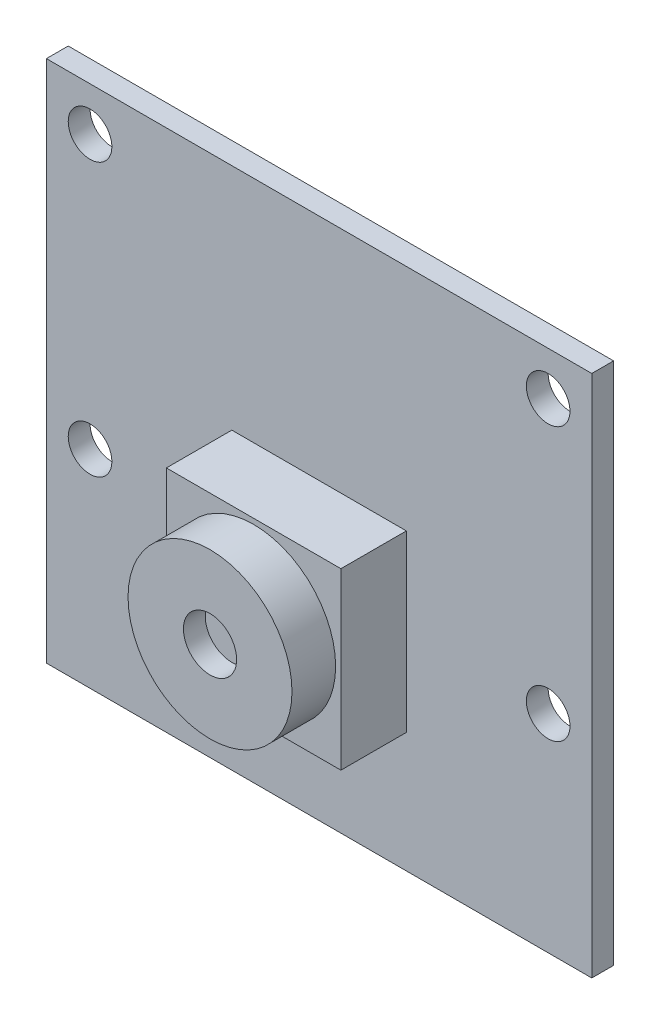
SolidWorks part; units mm, degrees
ref_plane "Front Plane" through (0, 0, 0) normal (0, 0, 1) x (1, 0, 0)
ref_plane "Top Plane" through (0, 0, 0) normal (0, 1, 0) x (1, 0, 0)
ref_plane "Right Plane" through (0, 0, 0) normal (1, 0, 0) x (0, 0, -1)
ref_axis "Axis1" through (-13.75, 0, 0) along (1, 0, 0)
ref_axis "Axis2" through (0, 13.2, 0) along (0, -1, 0)
ref_axis "Axis3" through (0, 0, 6.3) along (0, 0, -1)
ref_point "Point1"
sketch "Sketch1" plane through (0, 0, 0) normal (0, 0, 1) x (1, 0, 0)
  line L1 (-12.5, -12) -> (12.5, -12)
  line L2 (-12.5, -12) -> (-12.5, 12)
  line L3 (-12.5, 12) -> (12.5, 12)
  line L4 (12.5, -12) -> (12.5, 12)
  line L5 (-12.5, -12) -> (12.5, 12) construction
  line L6 (-12.5, 12) -> (12.5, -12) construction
  point P0 (0, 0)
  dimension "D1" = 25
  dimension "D2" = 24
extrude "Boss-Extrude1" add sketch "Sketch1" along normal blind 1
sketch "Sketch2" plane through (0, 0, 1) normal (0, 0, 1) x (1, 0, 0)
  line L0 (-12.5, -12) -> (12.5, -12) construction
  line L1 (-4, -6.5) -> (4, -6.5)
  line L2 (-4, -6.5) -> (-4, 1.5)
  line L3 (-4, 1.5) -> (4, 1.5)
  line L4 (4, -6.5) -> (4, 1.5)
  line L5 (-4, -6.5) -> (4, 1.5) construction
  line L6 (-4, 1.5) -> (4, -6.5) construction
  line L7 (-12.5, 12) -> (-12.5, -12) construction
  point P0 (0, -2.5)
  dimension "D1" = 8
  dimension "D2" = 5.5
  dimension "D3" = 8.5
extrude "Boss-Extrude2" add sketch "Sketch2" along normal blind 3 separate body
sketch "Sketch3" plane through (0, 0, 4) normal (0, 0, 1) x (1, 0, 0)
  line L0 (-4, -6.5) -> (4, 1.5) construction
  line L1 (4, -6.5) -> (4, 1.5) construction
  line L2 (4, 1.5) -> (-4, 1.5) construction
  circle A0 centre (0, -2.5) radius 3.7578
extrude "Boss-Extrude3" add sketch "Sketch3" along normal blind 2 separate body
sketch "Sketch4" plane through (0, 0, 6) normal (0, 0, 1) x (1, 0, 0)
  circle A0 centre (0, -2.5) radius 1.219
extrude "Cut-Extrude1" cut sketch "Sketch4" against normal blind 1
sketch "Sketch5" plane through (0, 0, 1) normal (0, 0, 1) x (1, 0, 0)
  line L0 (-12.5, -12) -> (12.5, -12) construction
  line L1 (-10.5, 10) -> (10.5, 10) construction
  line L2 (-10.5, 10) -> (-10.5, -2.5) construction
  line L3 (-10.5, -2.5) -> (10.5, -2.5) construction
  line L4 (10.5, 10) -> (10.5, -2.5) construction
  line L5 (-10.5, 10) -> (10.5, -2.5) construction
  line L6 (-10.5, -2.5) -> (10.5, 10) construction
  line L7 (12.5, 12) -> (-12.5, 12) construction
  line L8 (0, 10) -> (0, 12) construction
  circle A0 centre (-10.5, -2.5) radius 1
  circle A1 centre (-10.5, 10) radius 1
  circle A2 centre (10.5, 10) radius 1
  circle A3 centre (10.5, -2.5) radius 1
  point P0 (0, 3.75)
  dimension "D4" = 2
  dimension "D1" = 9.5
  dimension "D2" = 2
  dimension "D3" = 21
extrude "Cut-Extrude2" cut sketch "Sketch5" against normal through all both and the other way through all
